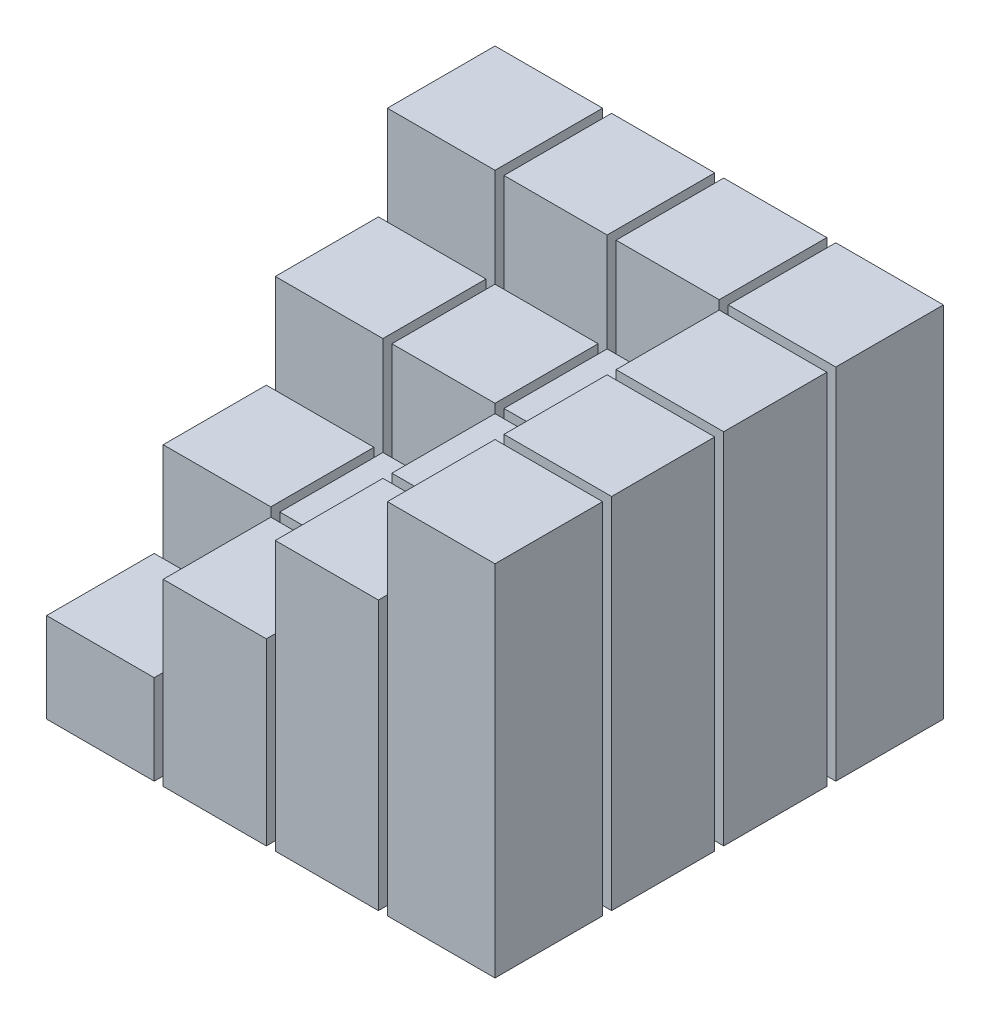
SolidWorks part; units mm, degrees
ref_plane "Front Plane" through (0, 0, 0) normal (0, 0, 1) x (1, 0, 0)
ref_plane "Top Plane" through (0, 0, 0) normal (0, 1, 0) x (1, 0, 0)
ref_plane "Right Plane" through (0, 0, 0) normal (1, 0, 0) x (0, 0, -1)
sketch "Sketch1" plane through (0, 0, 0) normal (0, 1, 0) x (1, 0, 0)
  line L1 (12.5, -12.5) -> (-12.5, -12.5)
  line L2 (12.5, -12.5) -> (12.5, 12.5)
  line L3 (12.5, 12.5) -> (-12.5, 12.5)
  line L4 (-12.5, -12.5) -> (-12.5, 12.5)
  line L5 (12.5, -12.5) -> (-12.5, 12.5) construction
  line L6 (12.5, 12.5) -> (-12.5, -12.5) construction
  point P0 (0, 0)
  dimension "D1" = 25
extrude "Boss-Extrude1" add sketch "Sketch1" along normal blind 5
sketch "Sketch2" plane through (0, 0, 0) normal (0, 1, 0) x (1, 0, 0)
  line L0 (-12.5, -12.5) -> (12.5, 12.5) construction
  line L1 (-12.5, 12.5) -> (12.5, 12.5)
  line L2 (-12.5, 12.5) -> (-12.5, -12.5)
  line L3 (-12.5, -12.5) -> (12.5, -12.5)
  line L4 (12.5, 12.5) -> (12.5, -12.5)
  line L6 (-12.5, -12.5) -> (-6.25, -12.5)
  line L7 (-12.5, -12.5) -> (-12.5, -6.25)
  line L8 (-12.5, -6.25) -> (-6.25, -6.25)
  line L9 (-6.25, -12.5) -> (-6.25, -6.25)
  line L10 (-12.5, -12.5) -> (0, -12.5)
  line L11 (-12.5, -12.5) -> (-12.5, 0)
  line L12 (-12.5, 0) -> (0, 0)
  line L13 (0, -12.5) -> (0, 0)
  line L14 (-12.5, -12.5) -> (6.25, -12.5)
  line L15 (-12.5, -12.5) -> (-12.5, 6.25)
  line L16 (-12.5, 6.25) -> (6.25, 6.25)
  line L17 (6.25, -12.5) -> (6.25, 6.25)
  point P6 (6.25, 6.25)
  point P7 (0, 0)
  point P8 (-6.25, -6.25)
  dimension "D1" = 6.25
  dimension "D2" = 6.25
extrude "Boss-Extrude2" add sketch "Sketch2" along normal blind 10 contours L8 L0 L12 L2 | L0 L9 L3 L13 | L12 L0 L16 L2 | L0 L13 L3 L17 | L16 L0 L1 L2 | L0 L17 L3 L4 region at (-7.6389, 0, 2.7778) region at (-2.7778, 0, 7.6389) region at (-4.5833, 0, -3.3333) region at (3.3333, 0, 4.5833) region at (-1.4881, 0, -9.5238) region at (9.5238, 0, 1.4881)
extrude "Boss-Extrude3" add sketch "Sketch2<3>" along normal blind 15 contours L12 L0 L16 L2 | L16 L0 L1 L2 | L0 L17 L3 L4 | L0 L13 L3 L17 region at (-4.5833, 0, -3.3333) region at (3.3333, 0, 4.5833) region at (-1.4881, 0, -9.5238) region at (9.5238, 0, 1.4881)
sketch "Sketch2<3>" plane through (0, 0, 0) normal (0, 1, 0) x (1, 0, 0) same geometry as "Sketch2"
extrude "Boss-Extrude4" add sketch "Sketch2<4>" along normal blind 20 contours L16 L0 L1 L2 | L0 L17 L3 L4 region at (-1.4881, 0, -9.5238) region at (9.5238, 0, 1.4881)
sketch "Sketch2<4>" plane through (0, 0, 0) normal (0, 1, 0) x (1, 0, 0) same geometry as "Sketch2"
sketch "Sketch3" plane through (0, 0, 0) normal (0, 1, 0) x (1, 0, 0)
  line L0 (-12.5, -6.25) -> (-6.5, -6.25) construction
  line L1 (12.5, 12.5) -> (12.5, -12.5) construction
  line L2 (-12.5, 0) -> (-6.5, 0) construction
  line L3 (-0.25, 6.25) -> (0, 6.25) construction
  line L4 (-6.25, -12.5) -> (-6.25, -6.5)
  line L5 (-12.5, 12.5) -> (12.5, 12.5) construction
  line L6 (0, -12.5) -> (0, -6.5) construction
  line L7 (6.25, -12.5) -> (6.25, -6.5) construction
  line L8 (-12.5, -0.25) -> (-6.5, -0.25)
  line L9 (-12.5, 6) -> (-6.5, 6)
  line L10 (-6, -12.5) -> (-6, -6.5)
  line L11 (0.25, -12.5) -> (0.25, -6.5)
  line L12 (6.5, -12.5) -> (6.5, -6.5)
  line L13 (-12.5, -6.5) -> (-6.5, -6.5)
  line L14 (-12.5, 0.25) -> (-6.5, 0.25)
  line L15 (-12.5, 6.5) -> (-6.5, 6.5)
  line L16 (-6.5, -12.5) -> (-6.5, -6.5)
  line L17 (-0.25, -12.5) -> (-0.25, -6.5)
  line L18 (6, -12.5) -> (6, -6.5)
  line L19 (-12.5, -6) -> (-6.5, -6)
  line L20 (-6.5, 6.25) -> (-6.5, 6.5) construction
  line L21 (-6.5, 6.5) -> (-6.5, 12.5)
  line L22 (-6.5, -12.5) -> (-6.5, 12.5) construction
  line L23 (-6.5, 6.5) -> (-6.25, 6.5) construction
  line L24 (-6, 6.5) -> (-0.25, 6.5)
  line L25 (-12.5, 6.5) -> (12.5, 6.5) construction
  line L26 (-6.25, 6.5) -> (-6, 6.5) construction
  line L27 (-6, 6.25) -> (-6, 6.5) construction
  line L28 (-6, 6.5) -> (-6, 12.5)
  line L29 (-6, -12.5) -> (-6, 12.5) construction
  line L30 (-6.25, 6.25) -> (-6.25, 6.5) construction
  line L31 (-6.25, 6.5) -> (-6.25, 12.5)
  line L32 (-6.25, -12.5) -> (-6.25, 12.5) construction
  line L33 (-12.5, 6.25) -> (-6.5, 6.25) construction
  line L34 (-12.5, 6.25) -> (12.5, 6.25) construction
  line L35 (-6.5, 6) -> (-6.5, 6.25) construction
  line L36 (-6.5, 6.25) -> (-6.25, 6.25) construction
  line L37 (-6.25, 6.25) -> (-6, 6.25) construction
  line L38 (-6, 6) -> (-6, 6.25) construction
  line L39 (-6.25, 6) -> (-6.25, 6.25) construction
  line L40 (-6.5, 6) -> (-6.25, 6) construction
  line L41 (-6, 6) -> (-0.25, 6)
  line L42 (-12.5, 6) -> (12.5, 6) construction
  line L43 (-6.25, 0.25) -> (-6.25, 6) construction
  line L44 (-6.25, 6) -> (-6, 6) construction
  line L45 (-0.25, 6.25) -> (-0.25, 6.5) construction
  line L46 (-0.25, 6.5) -> (-0.25, 12.5)
  line L47 (-0.25, -12.5) -> (-0.25, 12.5) construction
  line L48 (-0.25, 6.5) -> (0, 6.5) construction
  line L49 (0.25, 6.5) -> (6, 6.5)
  line L50 (0, 6.5) -> (0, 12.5) construction
  line L51 (0, -12.5) -> (0, 12.5) construction
  line L52 (0, 6.5) -> (0.25, 6.5) construction
  line L53 (0, 6.25) -> (0.25, 6.25) construction
  line L54 (6, 6.25) -> (6.25, 6.25) construction
  line L55 (0.25, 6.25) -> (0.25, 6.5) construction
  line L56 (0.25, 6.5) -> (0.25, 12.5)
  line L57 (0.25, -12.5) -> (0.25, 12.5) construction
  line L58 (0, 6.25) -> (0, 6.5) construction
  line L59 (-6, 6.25) -> (-0.25, 6.25) construction
  line L60 (-0.25, 6) -> (-0.25, 6.25) construction
  line L61 (0, 6) -> (0, 6.25) construction
  line L62 (0.25, 6) -> (0.25, 6.25) construction
  line L63 (0.25, 6.25) -> (6, 6.25) construction
  line L64 (-0.25, 6) -> (0, 6) construction
  line L65 (0.25, 6) -> (6, 6)
  line L66 (0, 0.25) -> (0, 6) construction
  line L67 (0, 6) -> (0.25, 6) construction
  line L68 (6, 6.25) -> (6, 6.5) construction
  line L69 (6, 6.5) -> (6, 12.5)
  line L70 (6, -12.5) -> (6, 12.5) construction
  line L71 (6, 6.5) -> (6.25, 6.5) construction
  line L72 (6.5, 6.5) -> (12.5, 6.5)
  line L73 (6.25, 6.5) -> (6.25, 12.5) construction
  line L74 (6.25, -12.5) -> (6.25, 12.5) construction
  line L75 (6.25, 6.5) -> (6.5, 6.5) construction
  line L76 (6.25, 6.25) -> (6.25, 6.5) construction
  line L77 (6.5, 6.25) -> (6.5, 6.5) construction
  line L78 (6.5, 6.5) -> (6.5, 12.5)
  line L79 (6.5, -12.5) -> (6.5, 12.5) construction
  line L80 (6.5, 6.25) -> (12.5, 6.25) construction
  line L81 (6.5, 6) -> (6.5, 6.25) construction
  line L82 (6.25, 6.25) -> (6.5, 6.25) construction
  line L83 (6.25, 6) -> (6.25, 6.25) construction
  line L84 (6, 6) -> (6, 6.25) construction
  line L85 (6, 6) -> (6.25, 6) construction
  line L86 (6.5, 6) -> (12.5, 6)
  line L87 (6.25, 0.25) -> (6.25, 6) construction
  line L88 (6.25, 6) -> (6.5, 6) construction
  line L89 (-6.5, 0) -> (-6.5, 0.25) construction
  line L90 (-6.5, 0.25) -> (-6.5, 6)
  line L91 (-6.5, 0.25) -> (-6.25, 0.25) construction
  line L92 (-6, 0.25) -> (-0.25, 0.25)
  line L93 (-12.5, 0.25) -> (12.5, 0.25) construction
  line L94 (-6.25, 0.25) -> (-6, 0.25) construction
  line L95 (-6.25, 0) -> (-6.25, 0.25) construction
  line L96 (-6, 0) -> (-6, 0.25) construction
  line L97 (-6, 0.25) -> (-6, 6)
  line L98 (-6.25, 0) -> (-6, 0) construction
  line L99 (-6, 0) -> (-0.25, 0) construction
  line L100 (-12.5, 0) -> (12.5, 0) construction
  line L101 (-6, -0.25) -> (-6, 0) construction
  line L102 (-6.25, -0.25) -> (-6.25, 0) construction
  line L103 (-6.5, 0) -> (-6.25, 0) construction
  line L104 (-6.5, -0.25) -> (-6.5, 0) construction
  line L105 (-6.5, -0.25) -> (-6.25, -0.25) construction
  line L106 (-6, -0.25) -> (-0.25, -0.25)
  line L107 (-12.5, -0.25) -> (12.5, -0.25) construction
  line L108 (-6.25, -0.25) -> (-6, -0.25) construction
  line L109 (-6.25, -6) -> (-6.25, -0.25) construction
  line L110 (-0.25, 0) -> (-0.25, 0.25) construction
  line L111 (-0.25, 0.25) -> (-0.25, 6)
  line L112 (-0.25, 0.25) -> (0, 0.25) construction
  line L113 (0.25, 0.25) -> (6, 0.25)
  line L114 (0, 0.25) -> (0.25, 0.25) construction
  line L115 (0.25, 0) -> (0.25, 0.25) construction
  line L116 (0.25, 0.25) -> (0.25, 6)
  line L117 (0, 0) -> (0, 0.25) construction
  line L118 (-0.25, 0) -> (0, 0) construction
  line L119 (0.25, 0) -> (6, 0) construction
  line L120 (-0.25, -0.25) -> (-0.25, 0) construction
  line L121 (0, 0) -> (0.25, 0) construction
  line L122 (0.25, -0.25) -> (0.25, 0) construction
  line L123 (0, -0.25) -> (0, 0) construction
  line L124 (-0.25, -0.25) -> (0, -0.25) construction
  line L125 (0.25, -0.25) -> (6, -0.25)
  line L126 (0, -6) -> (0, -0.25) construction
  line L127 (0, -0.25) -> (0.25, -0.25) construction
  line L128 (6, 0) -> (6, 0.25) construction
  line L129 (6, 0.25) -> (6, 6)
  line L130 (6, 0.25) -> (6.25, 0.25) construction
  line L131 (6.5, 0.25) -> (12.5, 0.25)
  line L132 (6.25, 0.25) -> (6.5, 0.25) construction
  line L133 (6.25, 0) -> (6.25, 0.25) construction
  line L134 (6.5, 0) -> (6.5, 0.25) construction
  line L135 (6.5, 0.25) -> (6.5, 6)
  line L136 (6.25, 0) -> (6.5, 0) construction
  line L137 (6.5, 0) -> (12.5, 0) construction
  line L138 (6.5, -0.25) -> (6.5, 0) construction
  line L139 (6.25, -0.25) -> (6.25, 0) construction
  line L140 (6, 0) -> (6.25, 0) construction
  line L141 (6, -0.25) -> (6, 0) construction
  line L142 (6, -0.25) -> (6.25, -0.25) construction
  line L143 (6.5, -0.25) -> (12.5, -0.25)
  line L144 (6.25, -6) -> (6.25, -0.25) construction
  line L145 (6.25, -0.25) -> (6.5, -0.25) construction
  line L146 (6, -6.25) -> (6, -6) construction
  line L147 (6, -6) -> (6, -0.25)
  line L148 (6, -6) -> (6.25, -6) construction
  line L149 (6.5, -6) -> (12.5, -6)
  line L150 (-12.5, -6) -> (12.5, -6) construction
  line L151 (6.25, -6) -> (6.5, -6) construction
  line L152 (6.25, -6.25) -> (6.25, -6) construction
  line L153 (6.5, -6.25) -> (6.5, -6) construction
  line L154 (6.5, -6) -> (6.5, -0.25)
  line L155 (6.25, -6.25) -> (6.5, -6.25) construction
  line L156 (6.5, -6.25) -> (12.5, -6.25) construction
  line L157 (-12.5, -6.25) -> (12.5, -6.25) construction
  line L158 (6.25, -6.5) -> (6.25, -6.25) construction
  line L159 (6, -6.5) -> (6, -6.25) construction
  line L160 (6.5, -6.5) -> (6.5, -6.25) construction
  line L161 (6.25, -6.5) -> (6.5, -6.5) construction
  line L162 (6.5, -6.5) -> (12.5, -6.5)
  line L163 (-12.5, -6.5) -> (12.5, -6.5) construction
  line L164 (6, -6.5) -> (6.25, -6.5) construction
  line L165 (-0.25, -6.25) -> (-0.25, -6) construction
  line L166 (-0.25, -6) -> (-0.25, -0.25)
  line L167 (0, -6.25) -> (0, -6) construction
  line L168 (0.25, -6.25) -> (0.25, -6) construction
  line L169 (0.25, -6) -> (0.25, -0.25)
  line L170 (0.25, -6.25) -> (6, -6.25) construction
  line L171 (6, -6.25) -> (6.25, -6.25) construction
  line L172 (0.25, -6.5) -> (0.25, -6.25) construction
  line L173 (0, -6.5) -> (0, -6.25) construction
  line L174 (-0.25, -6.5) -> (-0.25, -6.25) construction
  line L175 (-0.25, -6) -> (0, -6) construction
  line L176 (0.25, -6) -> (6, -6)
  line L177 (0, -6) -> (0.25, -6) construction
  line L178 (0, -6.5) -> (0.25, -6.5) construction
  line L179 (0.25, -6.5) -> (6, -6.5)
  line L180 (-0.25, -6.5) -> (0, -6.5) construction
  line L181 (-6.5, -6.25) -> (-6.5, -6) construction
  line L182 (-6.5, -6) -> (-6.5, -0.25)
  line L183 (-6.25, -6.25) -> (-6.25, -6) construction
  line L184 (-6, -6.25) -> (-6, -6) construction
  line L185 (-6, -6) -> (-6, -0.25)
  line L186 (-6.25, -6) -> (-6, -6) construction
  line L187 (-6, -6) -> (-0.25, -6)
  line L188 (-6.25, -6.25) -> (-6, -6.25) construction
  line L189 (-6, -6.25) -> (0.25, -6.25) construction
  line L190 (-6.25, -6.5) -> (-6, -6.5) construction
  line L191 (-6, -6.5) -> (-0.25, -6.5)
  line L192 (-6, -6.5) -> (-6, -6.25) construction
  line L193 (-6.25, -6.5) -> (-6.25, -6.25) construction
  line L194 (-6.5, -6.5) -> (-6.5, -6.25) construction
  line L195 (-6.5, -6.5) -> (-6.25, -6.5) construction
  line L196 (-6.5, -6) -> (-6.25, -6) construction
  line L197 (-6.5, -6.25) -> (-6.25, -6.25) construction
  arc A0 (-12.5, -0.25) -> (-12.5, 0.25) centre (-12.5, 0) cw
  arc A1 (12.5, -0.25) -> (12.5, 0.25) centre (12.5, 0) ccw
  arc A2 (-12.5, 6) -> (-12.5, 6.5) centre (-12.5, 6.25) cw
  arc A3 (12.5, 6) -> (12.5, 6.5) centre (12.5, 6.25) ccw
  arc A4 (-6, -12.5) -> (-6.5, -12.5) centre (-6.25, -12.5) cw
  arc A5 (-6, 12.5) -> (-6.5, 12.5) centre (-6.25, 12.5) ccw
  arc A6 (0.25, -12.5) -> (-0.25, -12.5) centre (0, -12.5) cw
  arc A7 (0.25, 12.5) -> (-0.25, 12.5) centre (0, 12.5) ccw
  arc A8 (6.5, -12.5) -> (6, -12.5) centre (6.25, -12.5) cw
  arc A9 (6.5, 12.5) -> (6, 12.5) centre (6.25, 12.5) ccw
  arc A10 (-12.5, -6.5) -> (-12.5, -6) centre (-12.5, -6.25) cw
  arc A11 (12.5, -6.5) -> (12.5, -6) centre (12.5, -6.25) ccw
  dimension "D1" = 0.25
  dimension "D2" = 0.25
extrude "Cut-Extrude1" cut sketch "Sketch3" along normal through all contours L162 A11 L149 L154 L143 A1 L131 L135 L86 A3 L72 L78 A9 L69 L49 L56 A7 L46 L24 L28 A5 L21 L15 A2 L9 L90 L14 A0 L8 L182 L19 A10 L13 L16 A4 L10 L191 L17 A6 L11 L179 L18 A8 L12 region at (0, 0, 0)
sketch "Sketch4" plane through (0, 0, 0) normal (0, 1, 0) x (1, 0, 0)
  line L0 (-12.5, -12.5) -> (-6.5, -6.5) construction
  circle A0 centre (-9.5, -9.5) radius 0.8
  circle A1 centre (-3.25, -9.5) radius 0.8
  circle A2 centre (3, -9.5) radius 0.8
  circle A3 centre (9.25, -9.5) radius 0.8
  circle A4 centre (-3.25, -3.25) radius 0.8
  circle A5 centre (3, -3.25) radius 0.8
  circle A6 centre (9.25, -3.25) radius 0.8
  circle A7 centre (-3.25, 3) radius 0.8
  circle A8 centre (3, 3) radius 0.8
  circle A9 centre (9.25, 3) radius 0.8
  circle A10 centre (-3.25, 9.25) radius 0.8
  circle A11 centre (3, 9.25) radius 0.8
  circle A12 centre (9.25, 9.25) radius 0.8
  circle A13 centre (-9.5, -3.25) radius 0.8
  circle A14 centre (-9.5, 3) radius 0.8
  circle A15 centre (-9.5, 9.25) radius 0.8
  dimension "D1" = 1.6
  dimension "D2" = 4
  dimension "D3" = 4
extrude "Cut-Extrude2" cut sketch "Sketch4" along normal blind 4
